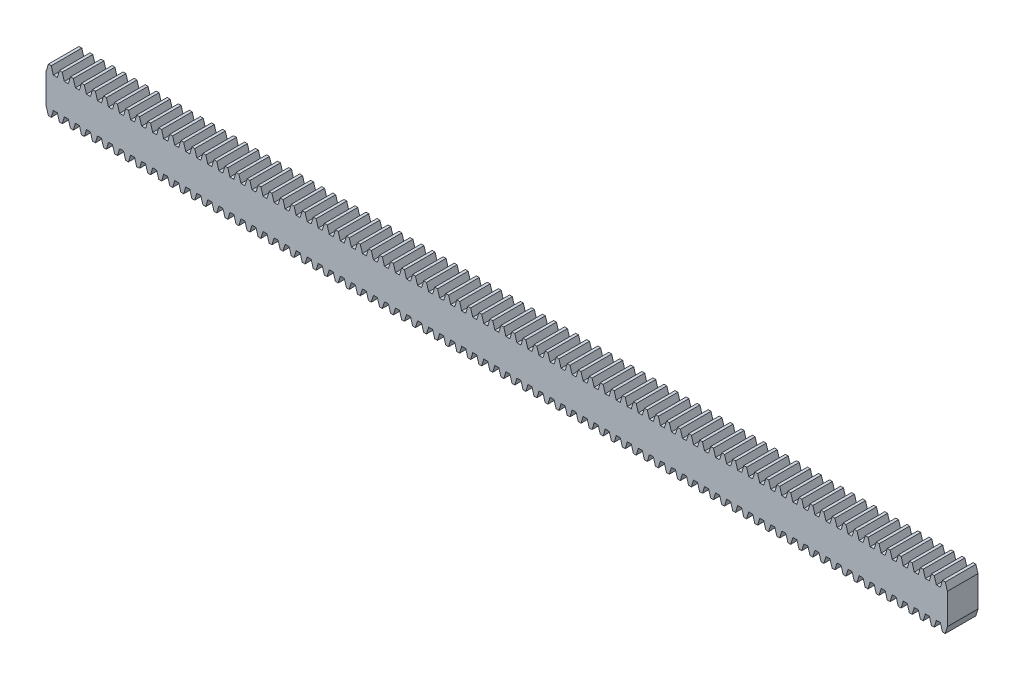
SolidWorks part; units mm, degrees
ref_plane "Front Plane" through (0, 0, 0) normal (0, 0, 1) x (1, 0, 0)
ref_plane "Top Plane" through (0, 0, 0) normal (0, 1, 0) x (1, 0, 0)
ref_plane "Right Plane" through (0, 0, 0) normal (1, 0, 0) x (0, 0, -1)
sketch "Sketch1" plane through (0, 0, 0) normal (0, 0, 1) x (1, 0, 0)
  line L0 (0, 92.625) -> (0, -82.875) construction
  line L1 (-144.1818, 0) -> (138.8636, 0) construction
  line L3 (-191.5, 6.5) -> (191.5, 6.5)
  line L4 (-191.5, 6.5) -> (-191.5, -6.5)
  line L5 (-191.5, -6.5) -> (191.5, -6.5)
  line L6 (191.5, 6.5) -> (191.5, -6.5)
  dimension "D1" = 13
  dimension "D2" = 383
extrude "Boss-Extrude1" add sketch "Sketch1" along normal blind 13
sketch "Sketch2" plane through (0, 0, 0) normal (0, 0, -1) x (-1, 0, 0)
  line L0 (-191.5, 6.5) -> (-190.6, 9.5)
  line L1 (-190.6, 9.5) -> (-189.4, 9.5)
  line L2 (-189.4, 9.5) -> (-188.5, 6.5)
  line L3 (-191.5, 6.5) -> (191.5, 6.5) construction
  line L4 (-188.5, 6.5) -> (-191.5, 6.5)
  line L5 (212.4782, 0) -> (-258.2951, 0) construction
  line L6 (-188.5, -6.5) -> (-191.5, -6.5)
  line L7 (-189.4, -9.5) -> (-188.5, -6.5)
  line L8 (-190.6, -9.5) -> (-189.4, -9.5)
  line L9 (-191.5, -6.5) -> (-190.6, -9.5)
  dimension "D1" = 3
  dimension "D2" = 3
  dimension "D3" = 1.2
extrude "Boss-Extrude3" add sketch "Sketch2" against normal up to surface (13 mm away) up to face at (0, 0, 13)
pattern_linear "LPattern1" count 82 spacing 4.69 along (-1, 0, 0) of "Boss-Extrude3"
sketch "Sketch4" plane through (0, 0, 0) normal (0, 0, -1) x (-1, 0, 0)
  line L0 (-191.5, -6.5) -> (-191.5, 6.5) construction
  line L1 (-187.5, 4.5) -> (187.5, 4.5)
  line L2 (-187.5, 4.5) -> (-187.5, -4.5)
  line L3 (-187.5, -4.5) -> (187.5, -4.5)
  line L4 (187.5, 4.5) -> (187.5, -4.5)
  line L5 (-170.64, 9.5) -> (-171.84, 9.5) construction
  line L6 (-171.84, -9.5) -> (-170.64, -9.5) construction
  line L7 (191.5, 6.5) -> (191.5, -6.5) construction
  dimension "D1" = 4
  dimension "D2" = 5
  dimension "D3" = 5
  dimension "D4" = 4
extrude "Cut-Extrude1" cut sketch "Sketch4" against normal blind 8
